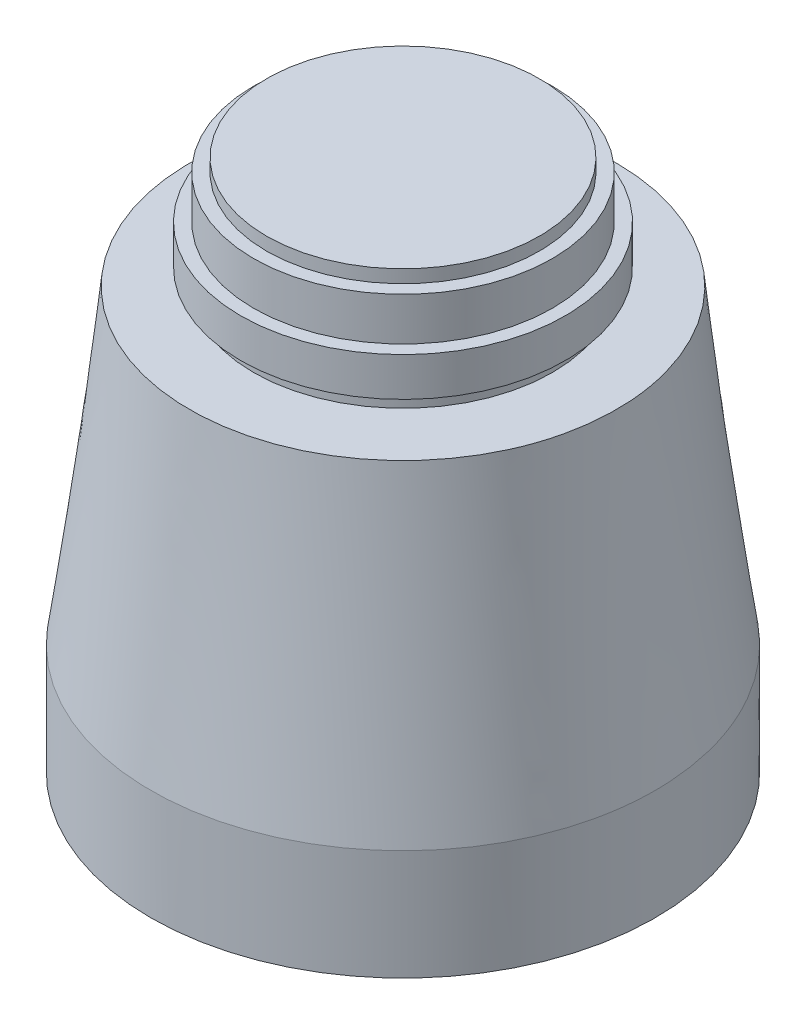
SolidWorks part; units mm, degrees
ref_plane "Front Plane" through (0, 0, 0) normal (0, 0, 1) x (1, 0, 0)
ref_plane "Top Plane" through (0, 0, 0) normal (0, 1, 0) x (1, 0, 0)
ref_plane "Right Plane" through (0, 0, 0) normal (1, 0, 0) x (0, 0, -1)
sketch "Sketch1" plane through (0, 0, 0) normal (0, 1, 0) x (1, 0, 0)
  circle A0 centre (0, 0) radius 19.5
  dimension "D1" = 39
extrude "Boss-Extrude1" add sketch "Sketch1" along normal blind 32.53
sketch "Sketch2" plane through (0, 32.53, 0) normal (0, 1, 0) x (1, 0, 0)
  circle A0 centre (0, 0) radius 11.55
  dimension "D1" = 23.1
extrude "Boss-Extrude2" add sketch "Sketch2" along normal blind 8.63
sketch "Sketch3" plane through (0, 41.16, 0) normal (0, 1, 0) x (1, 0, 0)
  circle A0 centre (0, 0) radius 12.55
  circle A1 centre (0, 0) radius 11.55 construction
  dimension "D1" = 1
extrude "Boss-Extrude3" add sketch "Sketch3" against normal blind 3 from offset 4.33 offset against normal yes
sketch "Sketch4" plane through (0, 41.16, 0) normal (0, 1, 0) x (1, 0, 0)
  circle A0 centre (0, 0) radius 10.55
  circle A1 centre (0, 0) radius 11.55 construction
  circle A2 centre (0, 0) radius 11.55
  dimension "D1" = 1
extrude "Cut-Extrude1" cut sketch "Sketch4" against normal blind 1
sketch "Sketch5" plane through (0, 32.53, 0) normal (0, 1, 0) x (1, 0, 0)
  circle A0 centre (0, 0) radius 16.5
  circle A1 centre (0, 0) radius 19.5 construction
  circle A2 centre (0, 0) radius 19.5
  dimension "D1" = 33
extrude "Cut-Extrude3" cut sketch "Sketch5" against normal blind 24
loft "Loft1" add section edge at (0, 8.53, 19.5) section edge at (0, 32.53, 16.5) connector at (-19.275, 8.53, 2.9536) connector at (-16.4507, 32.53, -1.2739)
